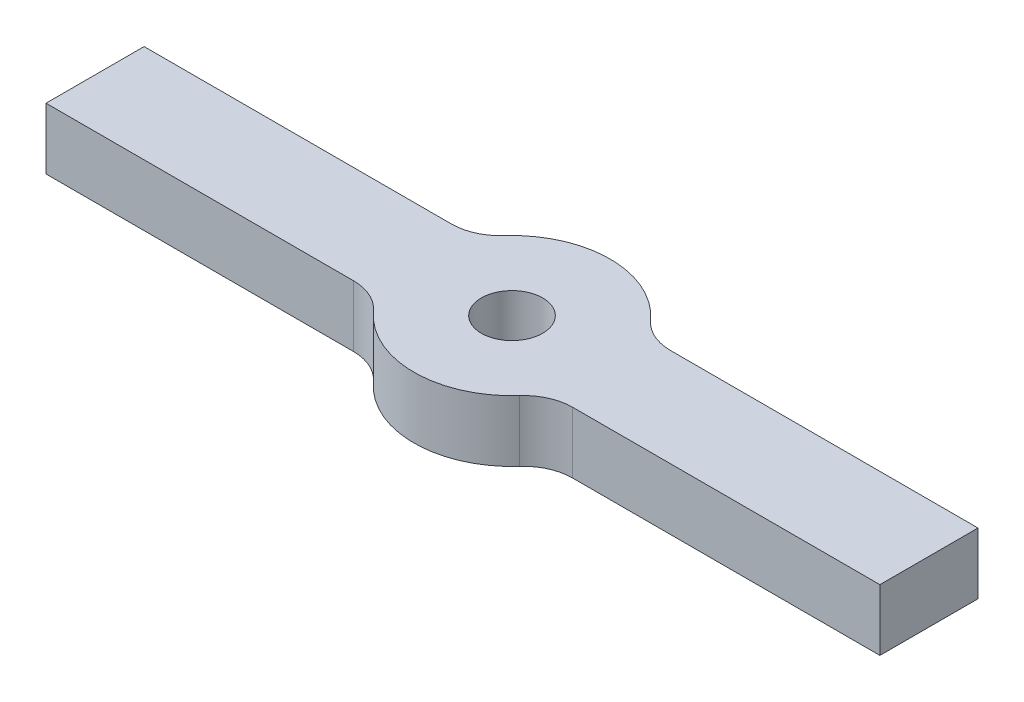
SolidWorks part; units mm, degrees
ref_plane "Front Plane" through (0, 0, 0) normal (0, 0, 1) x (1, 0, 0)
ref_plane "Top Plane" through (0, 0, 0) normal (0, 1, 0) x (1, 0, 0)
ref_plane "Right Plane" through (0, 0, 0) normal (1, 0, 0) x (0, 0, -1)
sketch "Sketch2" plane through (0, 0, 0) normal (0, 1, 0) x (1, 0, 0)
  line L0 (-21.997, 0) -> (0, 0) construction
  line L1 (-107.95, -25.4) -> (-21.997, -25.4)
  line L2 (-107.95, -25.4) -> (-107.95, 0)
  line L3 (-107.95, 0) -> (-21.997, 0)
  line L4 (-21.997, -25.4) -> (-21.997, 0)
  line L5 (21.997, -25.4) -> (107.95, -25.4)
  line L6 (21.997, -25.4) -> (21.997, 0)
  line L7 (21.997, 0) -> (107.95, 0)
  line L8 (107.95, -25.4) -> (107.95, 0)
  line L9 (0, 0) -> (21.997, 0) construction
  circle A0 centre (0, -12.7) radius 7.9375
  circle A1 centre (0, -12.7) radius 25.4
  point P11 (0, 0)
  point P13 (107.95, -12.7)
  point P15 (0, 0)
  dimension "D3" = 215.9
  dimension "D4" = 15.875
  dimension "D5" = 50.8
  dimension "D1" = 25.4
  dimension "D2" = 25.4
extrude "Boss-Extrude1" add sketch "Sketch2" along normal blind 15.875 contours A1 L3 L2 L1 | L4 A1 | L6 A1 L4 A0 | L6 A1 | A1 L5 L8 L7 region at (-66.1179, 0, 12.7) region at (-23.3664, 0, 12.7) region at (-21.325, 0, 12.7) region at (66.1179, 0, 12.7) region at (23.3664, 0, 12.7)
fillet "Fillet1" radius 12.7 4 edges at (21.997, 7.9375, 0) (21.997, 7.9375, 25.4) (-21.997, 7.9375, 25.4) (-21.997, 7.9375, 0)
